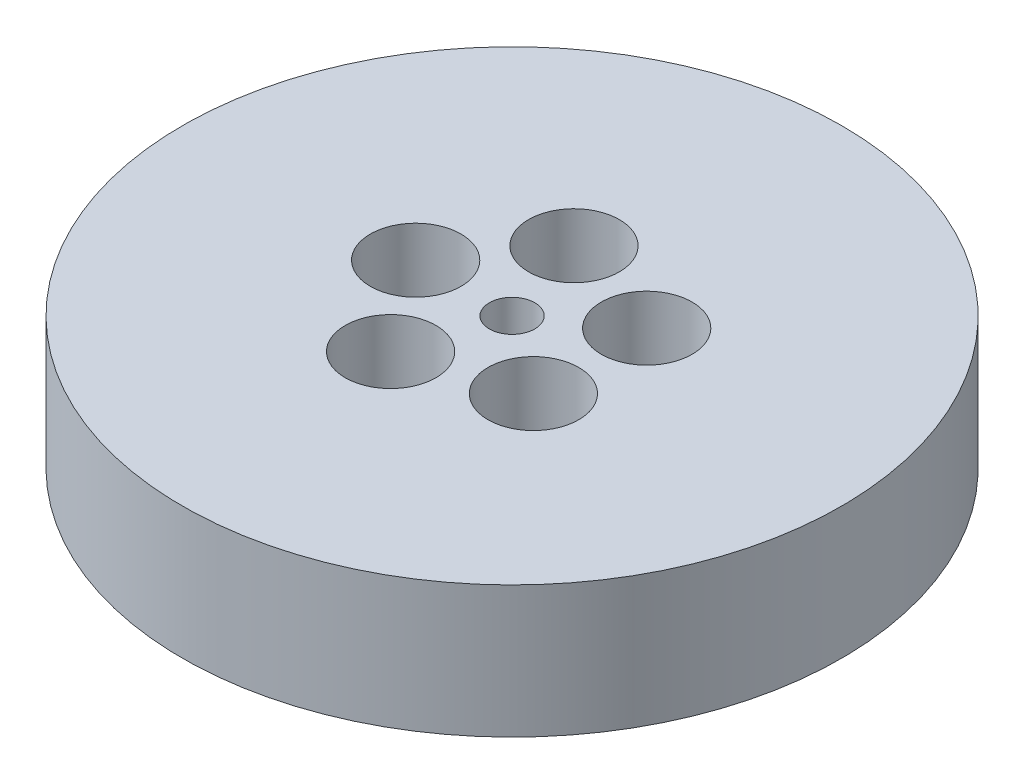
SolidWorks part; units mm, degrees
ref_plane "Front Plane" through (0, 0, 0) normal (0, 0, 1) x (1, 0, 0)
ref_plane "Top Plane" through (0, 0, 0) normal (0, 1, 0) x (1, 0, 0)
ref_plane "Right Plane" through (0, 0, 0) normal (1, 0, 0) x (0, 0, -1)
sketch "Sketch1" plane through (0, 0, 0) normal (0, 1, 0) x (1, 0, 0)
  circle A0 centre (0, 0) radius 72.5
  dimension "FLANGE_OD" = 145
extrude "Boss-Extrude1" add sketch "Sketch1" along normal blind 29
sketch "Sketch2" plane through (0, 0, 0) normal (0, 1, 0) x (1, 0, 0)
  circle A0 centre (0, 0) radius 5
  dimension "BORE_D" = 10
extrude "Cut-Extrude1" cut sketch "Sketch2" along normal through all
sketch "Sketch3" plane through (0, 29, 0) normal (0, 1, 0) x (1, 0, 0)
  circle A0 centre (0, 0) radius 21.2051 construction
  circle A1 centre (-21.2051, 0) radius 9.9783
  dimension "BOLT_D" = 19.9566
  dimension "BOLT_PCD" = 42.4102
extrude "Cut-Extrude2" cut sketch "Sketch3" against normal blind 28.597
pattern_circular "CirPattern1" count 5 over 360 about axis through (0, 0, 0) along (0, 1, 0) of "Cut-Extrude2"
